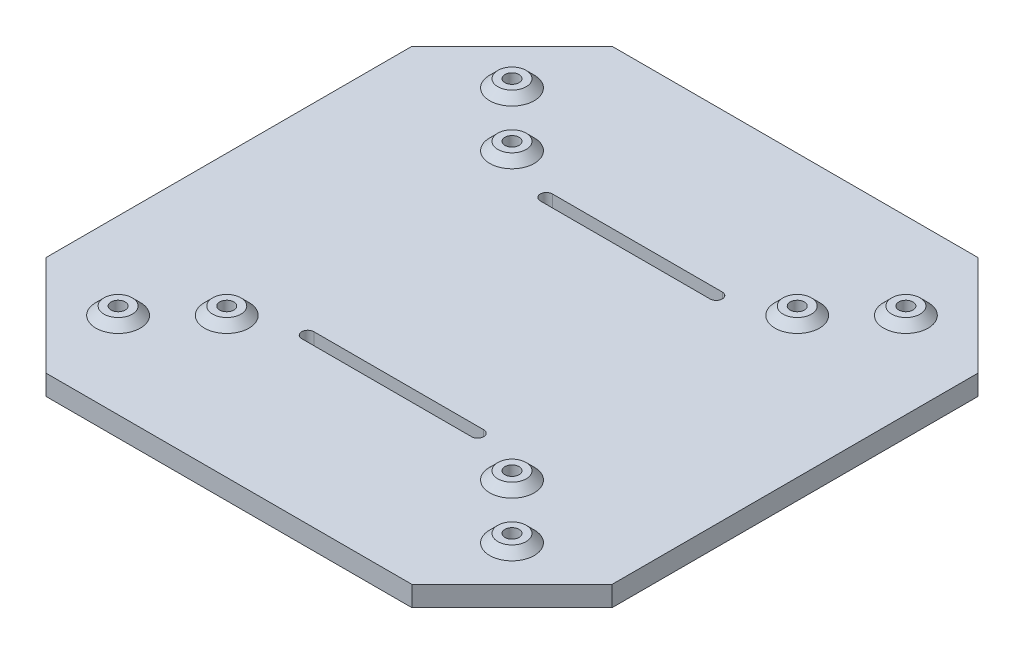
SolidWorks part; units mm, degrees
material "ABS generico"
ref_plane "Piano frontale" through (0, 0, 0) normal (0, 0, 1) x (1, 0, 0)
ref_plane "Piano superiore" through (0, 0, 0) normal (0, 1, 0) x (1, 0, 0)
ref_plane "Piano destro" through (0, 0, 0) normal (1, 0, 0) x (0, 0, -1)
sketch "Schizzo1" plane through (0, 0, 0) normal (0, 1, 0) x (1, 0, 0)
  line L1 (-25.9085, 30.6076) -> (114.0915, 30.6076)
  line L2 (-25.9085, 30.6076) -> (-25.9085, -109.3924)
  line L3 (-25.9085, -109.3924) -> (114.0915, -109.3924)
  line L4 (114.0915, 30.6076) -> (114.0915, -109.3924)
  dimension "D1" = 140
extrude "Estrusione-Estrusione1" add sketch "Schizzo1" along normal blind 5
sketch "Schizzo2" plane through (0, 5, 0) normal (0, 1, 0) x (1, 0, 0)
  line L0 (-1.1598, 30.6076) -> (-25.9085, 5.8589)
  line L1 (114.0915, 30.6076) -> (-25.9085, 30.6076) construction
  line L2 (-25.9085, 30.6076) -> (-25.9085, -109.3924) construction
  line L3 (-25.9085, 5.8589) -> (-25.9085, 30.6076)
  line L4 (-25.9085, 30.6076) -> (-1.1598, 30.6076)
  line L5 (44.0915, 30.6076) -> (44.0915, -109.3924) construction
  line L6 (-25.9085, -109.3924) -> (114.0915, -109.3924) construction
  line L7 (114.0915, -39.3924) -> (-25.9085, -39.3924) construction
  line L8 (114.0915, -109.3924) -> (114.0915, 30.6076) construction
  line L9 (114.0915, 5.8589) -> (89.3427, 30.6076)
  line L10 (89.3427, 30.6076) -> (114.0915, 30.6076)
  line L11 (114.0915, 30.6076) -> (114.0915, 5.8589)
  line L12 (89.3427, -109.3924) -> (114.0915, -84.6436)
  line L13 (114.0915, -84.6436) -> (114.0915, -109.3924)
  line L14 (114.0915, -109.3924) -> (89.3427, -109.3924)
  line L15 (-25.9085, -84.6436) -> (-1.1598, -109.3924)
  line L16 (-1.1598, -109.3924) -> (-25.9085, -109.3924)
  line L17 (-25.9085, -109.3924) -> (-25.9085, -84.6436)
  point P28 (44.0915, -39.3924)
  dimension "D1" = 45
  dimension "D2" = 35
  dimension "D3" = 4
extrude "Taglio-Estrusione1" cut sketch "Schizzo2" against normal through all
sketch "Schizzo3" plane through (0, 5, 0) normal (0, 1, 0) x (1, 0, 0)
  line L0 (114.0915, -39.3924) -> (-25.9085, -39.3924) construction
  line L1 (66.5915, -67.3924) -> (21.5915, -67.3924) construction
  line L2 (66.5915, -67.3924) -> (66.5915, -70.3924) construction
  line L3 (66.5915, -70.3924) -> (21.5915, -70.3924) construction
  line L4 (21.5915, -67.3924) -> (21.5915, -70.3924) construction
  line L5 (66.5915, -11.3924) -> (21.5915, -11.3924) construction
  line L6 (66.5915, -11.3924) -> (66.5915, -8.3924) construction
  line L7 (66.5915, -8.3924) -> (21.5915, -8.3924) construction
  line L8 (21.5915, -11.3924) -> (21.5915, -8.3924) construction
  line L9 (114.0915, -84.6436) -> (114.0915, 5.8589) construction
  line L10 (-25.9085, 5.8589) -> (-25.9085, -84.6436) construction
  line L11 (44.0915, 30.6076) -> (44.0915, -109.3924) construction
  line L12 (89.3427, 30.6076) -> (-1.1598, 30.6076) construction
  line L13 (-1.1598, -109.3924) -> (89.3427, -109.3924) construction
  line L14 (64.985, -67.3924) -> (23.0915, -67.3924)
  line L15 (23.0915, -70.3924) -> (64.985, -70.3924)
  line L16 (65.0915, -8.3924) -> (23.0915, -8.3924)
  line L17 (23.0915, -11.3924) -> (65.0915, -11.3924)
  arc A0 (64.985, -67.3924) -> (64.985, -70.3924) centre (65.0915, -68.8924) cw
  arc A1 (65.0915, -8.3924) -> (65.0915, -11.3924) centre (65.0915, -9.8924) cw
  arc A2 (23.0915, -8.3924) -> (23.0915, -11.3924) centre (23.0915, -9.8924) ccw
  arc A3 (23.0915, -67.3924) -> (23.0915, -70.3924) centre (23.0915, -68.8924) ccw
  dimension "D7" = 1.5
  dimension "D10" = 1.5
  dimension "D12" = 1.5
  dimension "D14" = 1.5
  dimension "D1" = 3
  dimension "D2" = 45
  dimension "D3" = 28
  dimension "D4" = 28
  dimension "D5" = 22.5
  dimension "D6" = 3
  dimension "D8" = 1.5
  dimension "D9" = 3
  dimension "D11" = 1.5
  dimension "D13" = 1.5
extrude "Taglio-Estrusione2" cut sketch "Schizzo3" against normal through all
sketch "Schizzo4" plane through (0, 5, 0) normal (0, 1, 0) x (1, 0, 0)
  line L0 (44.0915, 30.6076) -> (44.0915, -109.3924) construction
  line L3 (89.3427, 30.6076) -> (-1.1598, 30.6076) construction
  line L6 (-1.1598, -109.3924) -> (89.3427, -109.3924) construction
  line L7 (114.0915, -39.3924) -> (-25.9085, -39.3924) construction
  line L8 (114.0915, -84.6436) -> (114.0915, 5.8589) construction
  line L9 (-25.9085, 5.8589) -> (-25.9085, -84.6436) construction
  circle A0 centre (-4.6171, -88.1009) radius 5.5
  circle A1 centre (8.818, -74.6659) radius 5.5
  arc A5 (-2.7685, -84.8382) -> (-7.8798, -89.9494) centre (-4.6171, -88.1009) ccw construction
  circle A6 centre (8.818, -74.6659) radius 1.75 construction
  circle A7 centre (-4.6171, 9.3161) radius 5.5
  circle A8 centre (8.818, -4.1189) radius 5.5
  circle A9 centre (92.8, 9.3161) radius 5.5
  circle A10 centre (79.365, -4.1189) radius 5.5
  circle A11 centre (92.8, -88.1009) radius 5.5
  circle A12 centre (79.365, -74.6659) radius 5.5
  point P36 (44.0915, -39.3924)
  dimension "D1" = 11
extrude "Estrusione-Estrusione2" add sketch "Schizzo4" along normal blind 2
chamfer "Smusso1" distance 2 angle 45 8 edges at (8.818, 7, 80.1659) (-4.6171, 7, 93.6009) (-4.6171, 7, -3.8161) (8.818, 7, 9.6189) (92.8, 7, -3.8161) (79.365, 7, 9.6189) (92.8, 7, 93.6009) (79.365, 7, 80.1659)
sketch "Schizzo5" plane through (0, 7, 0) normal (0, 1, 0) x (1, 0, 0)
  line L0 (-4.6171, -88.1009) -> (93.2318, 11.1622) construction
  line L1 (-5.7565, 10.4494) -> (93.9389, -87.8256) construction
  circle A0 centre (-4.6171, -88.1009) radius 1.75
  circle A1 centre (8.818, -74.6659) radius 1.75
  circle A2 centre (-4.6171, 9.3161) radius 1.75
  circle A3 centre (8.818, -4.1189) radius 1.75
  circle A4 centre (92.8, 9.3161) radius 1.75
  circle A5 centre (79.365, -4.1189) radius 1.75
  circle A6 centre (92.8, -88.1009) radius 1.75
  circle A7 centre (79.365, -74.6659) radius 1.75
  circle A9 centre (-4.6171, -88.1009) radius 3.5 construction
  circle A10 centre (8.818, -74.6659) radius 3.5 construction
  point P26 (44.0915, -39.3924)
  dimension "D1" = 3.5
  dimension "D2" = 4
extrude "Taglio-Estrusione3" cut sketch "Schizzo5" against normal through all
